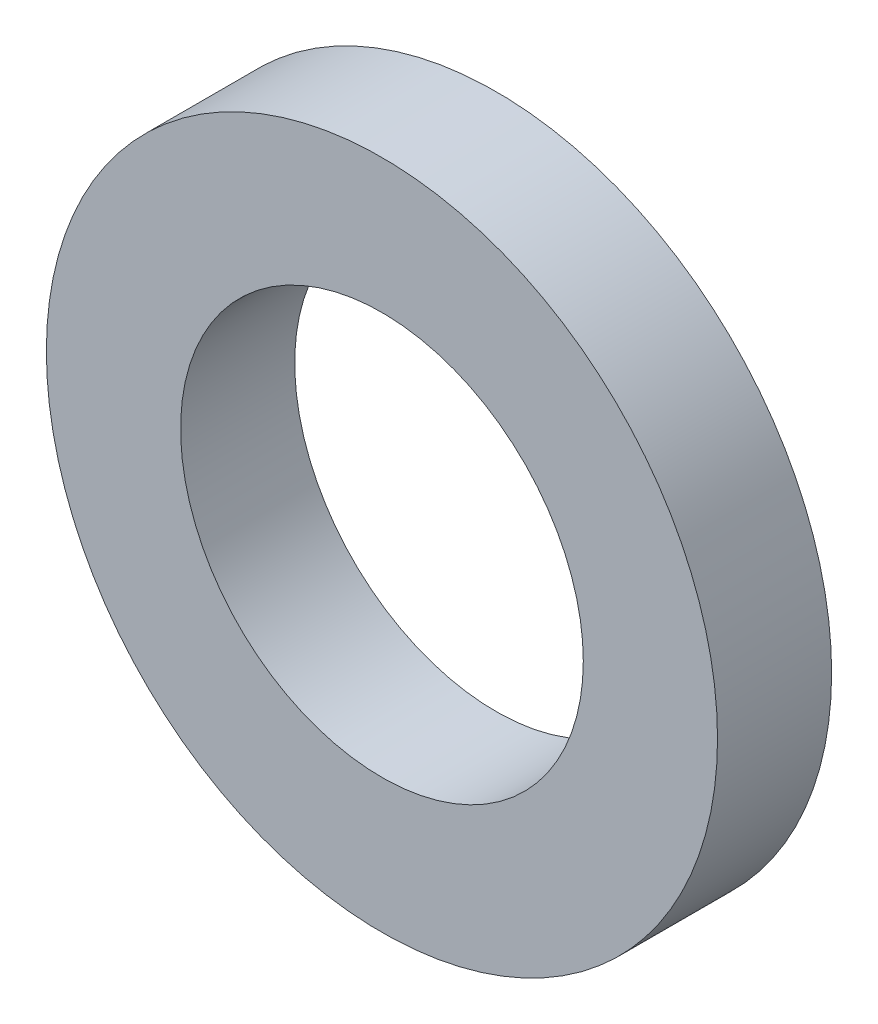
SolidWorks part; units mm, degrees
ref_plane "Front Plane" through (0, 0, 0) normal (0, 0, 1) x (1, 0, 0)
ref_plane "Top Plane" through (0, 0, 0) normal (0, 1, 0) x (1, 0, 0)
ref_plane "Right Plane" through (0, 0, 0) normal (1, 0, 0) x (0, 0, -1)
sketch "Sketch1" plane through (0, 0, 0) normal (0, 0, 1) x (1, 0, 0)
  circle A0 centre (0, 0) radius 3
  circle A1 centre (0, 0) radius 5
  dimension "D1" = 6
  dimension "D2" = 10
extrude "Boss-Extrude1" add sketch "Sketch1" along normal blind 1.7
equation "\"smallPulleyTeeth\"= 15"
equation "\"largePulleyTeeth\"= 40"
equation "\"eighthThick\"= 2.9mm"
equation "\"sixteenthThick\" = 1.7mm"
equation "\"quarterThick\"=5.9mm"
equation "\"OD\" = 145mm"
equation "\"puckAngle\" = 60.5deg"
equation "\"puckDiam\" = 76.5mm"
equation "\"axlePress\" = 5.9mm"
equation "\"press\" = 0.2mm"
equation "\"wheelClear\" = 0.3mm"
equation "\"10-32clear\" = 4.5mm"
equation "\"6-32clear\" = 3.3mm"
equation "\"8-32clear\" = 4.0mm"
equation "\"D1@Boss-Extrude1\"=\"sixteenthThick\""
